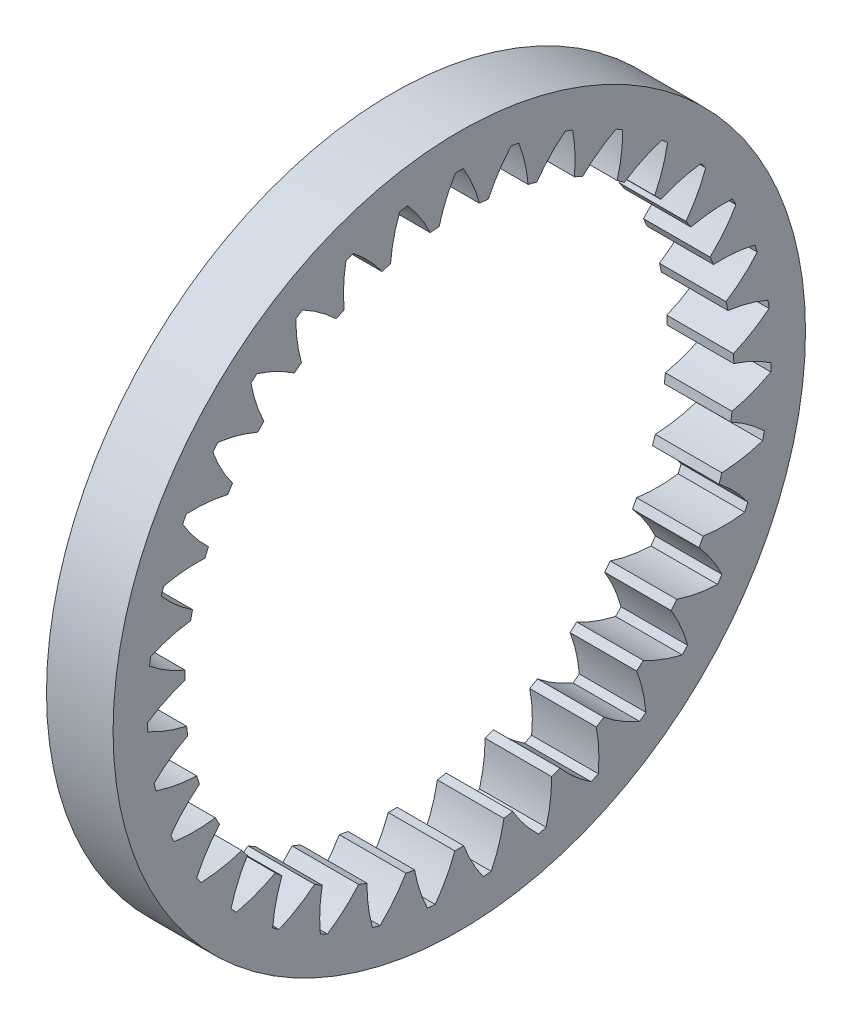
SolidWorks part; units mm, degrees
ref_plane "Plane1" through (0, 0, 0) normal (0, 0, 1) x (1, 0, 0)
ref_plane "Plane2" through (0, 0, 0) normal (0, 1, 0) x (1, 0, 0)
ref_plane "Plane3" through (0, 0, 0) normal (1, 0, 0) x (0, 0, -1)
sketch "HoldingSke" plane through (0, 0, 0) normal (0, 1, 0) x (1, 0, 0)
  line L0 (0, 0) -> (0.3277, -0.2294)
  line L1 (-15, 0) -> (100, 0) construction
  line L2 (0, 0) -> (-2.1039, 2.3779)
  line L3 (0, 0) -> (-11.863, 4.5341)
  line L4 (0, 0) -> (7.0742, 4.9534)
  line L5 (0, 0) -> (-23.7986, -8.8762)
  line L6 (0, 0) -> (-10.5278, -7.1032)
  line L7 (-2.1039, 2.3779) -> (3.3635, 27.1825)
  line L8 (-76.2, 4.8779) -> (-54.61, 4.8779)
  line L9 (-71.009, 38.7566) -> (-53.1078, 45.2721)
  line L10 (-76.2, 71.12) -> (104.1128, 71.12)
  line L11 (0, 0) -> (-10, 0)
  line L12 (-76.2, 101.6) -> (-76.113, 101.6)
  line L13 (24.9733, 27.94) -> (52.9518, 28.4284)
  line L14 (24.9733, 27.94) -> (24.9743, 27.94)
  line L15 (24.9733, 27.94) -> (100.4006, 29.5858)
  circle A0 centre (0, 0) radius 52
  circle A1 centre (0, 0) radius 12.7
  circle A2 centre (0, 0) radius 12.7
  dimension "Num_teeth" = 35
  dimension "Pitch_radius" = 180.3128
  dimension "Width" = 10
  dimension "Diameter" = 104
sketch "BasProSke" plane through (0, 0, 0) normal (0, 1, 0) x (1, 0, 0)
  line L0 (-10, 0) -> (60, 0) construction
  line L1 (0, 41.25) -> (0, 52)
  line L2 (0, 41.25) -> (10, 41.25)
  line L3 (10, 41.25) -> (10, 52)
  line L4 (10, 52) -> (0, 52)
  dimension "Thickness" = 10
  dimension "Diameter" = 104
revolve "Base-Revolve" add sketch "BasProSke" angle 360 about L0
sketch "TooCutSke" plane through (0, 0, 0) normal (1, 0, 0) x (0, 0, -1)
  line L3 (2.1803, 43.6956) -> (2.1803, 53.6633) construction
  line L4 (0, 0) -> (0, 59.563) construction
  line L5 (0, 0) -> (-6.1248, 68.0524) construction
  line L6 (-18.1095, 35.5201) -> (34.3738, 40.2436) construction
  circle A0 centre (0, 0) radius 43.75 construction
  circle A1 centre (0, 0) radius 46.876 construction
  circle A2 centre (0, 0) radius 37.0004 construction
  circle A3 centre (0, 0) radius 41.2246 construction
  arc A4 (3.0386, 41.1125) -> (0.5893, 46.8723) centre (-18.1095, 35.5201) ccw
  arc A5 (3.0386, 41.1125) -> (-3.0386, 41.1125) centre (0, 0) ccw
  arc A6 (0.5893, 46.8723) -> (-0.5893, 46.8723) centre (0, 0) ccw
  arc A7 (-0.5893, 46.8723) -> (-3.0386, 41.1125) centre (18.1095, 35.5201) ccw
extrude "ToothCut" cut sketch "TooCutSke" along normal through all
fillet "Breaks" [suppressed] radius 0.25
fillet "RootFillets" [suppressed] radius 0.626
pattern_circular "TeethCuts" count 35 every 10.286 about axis through (-10, 0, 0) along (1, 0, 0) of "RootFillets", "Breaks", "ToothCut"
equation "' \"Module@HoldingSke\" = 6.35"
equation "' \"Num_teeth@HoldingSke\" = 24"
equation "' \"Ap@HoldingSke\" =  14.5"
equation "' \"Ap@HoldingSke\" = 14.5"
equation "' \"Width@HoldingSke\" = 12"
equation "' \"Diameter@HoldingSke\" = 8 * 25.4"
equation "' \"Show_teeth@HoldingSke\" = 100"
equation "' \"Backlash@HoldingSke\" = 0.009 * 25.4"
equation "' \"Addendum_fac@HoldingSke\" = 1.0"
equation "' \"Dedendum_fac@HoldingSke\" = 1.25"
equation "' \"Dedendum_add@HoldingSke\" = 0.00005 * 25.4"
equation "' \"Clearance_fac@HoldingSke\" = 0.25"
equation "\"Pitch@HoldingSke\" = 1 / \"Module@HoldingSke\" "
equation "\"Overcut_dia@TooCutSke\" = (\"Num_teeth@HoldingSke\" - 2 * \"Addendum_fac@HoldingSke\") / \"Pitch@HoldingSke\" - 0.002 * 25.4"
equation "\"Pitch_dia@TooCutSke\" = \"Num_teeth@HoldingSke\" / \"Pitch@HoldingSke\""
equation "\"Base_dia@TooCutSke\" = \"Num_teeth@HoldingSke\" / \"Pitch@HoldingSke\" * cos((\"Ap@HoldingSke\"  * 3.14159265 / 180)) * 0.90"
equation "\"Root_dia@TooCutSke\" = \"Num_teeth@HoldingSke\"  / \"Pitch@HoldingSke\" + 2 *  \"Dedendum_fac@HoldingSke\"/ \"Pitch@HoldingSke\" + \"Dedendum_add@HoldingSke\" * 2"
equation "\"Half_ang@TooCutSke\" = 180 / \"Num_teeth@HoldingSke\""
equation "\"Half_CT@TooCutSke\" = \"Num_teeth@HoldingSke\" / \"Pitch@HoldingSke\" * sin((3.14159265 / 2 / \"Num_teeth@HoldingSke\")) / 2 + 10 * \"Backlash@HoldingSke\" / 4"
equation "\"Flank_rad@TooCutSke\" = \"Num_teeth@HoldingSke\" / \"Pitch@HoldingSke\" / 4"
equation "\"Radius@RootFillets\"= \"Clearance_fac@HoldingSke\" / \"Pitch@HoldingSke\" + \"Dedendum_add@HoldingSke\""
equation "\"Break_rad@Breaks\" = 0.02 / \"Pitch@HoldingSke\" * 5"
equation "\"Num_teeth@TeethCuts\" = int( \"Show_teeth@HoldingSke\" ) + 1"
equation "\"Num_teeth@TeethCuts\" = ((sgn( \"Num_teeth@TeethCuts\" - \"Num_teeth@HoldingSke\" )-1)*( \"Num_teeth@TeethCuts\" - \"Num_teeth@HoldingSke\" ))/-2+ \"Num_teeth@HoldingSke\""
equation "\"Num_teeth@TeethCuts\" = ((sgn( \"Num_teeth@TeethCuts\" - 2.0)+1)*( \"Num_teeth@TeethCuts\" - 2.0))/2 +2.0"
equation "\"Angle@TeethCuts\" = 360.0 / \"Num_teeth@HoldingSke\""
equation "\"Diameter@BasProSke\" = \"Num_teeth@HoldingSke\"  / \"Pitch@HoldingSke\" + 2 *  \"Dedendum_fac@HoldingSke\"/ \"Pitch@HoldingSke\" + \"Dedendum_add@HoldingSke\" * 2 + 0.002 * 25.4"
equation "\"Diameter@BasProSke\" = ((sgn( \"Diameter@BasProSke\"  - \"Diameter@HoldingSke\" )+1)*( \"Diameter@BasProSke\"  - \"Diameter@HoldingSke\" ))/2 + \"Diameter@HoldingSke\""
equation "\"Inside_diameter@BasProSke\" =  (\"Num_teeth@HoldingSke\" - 2 * \"Addendum_fac@HoldingSke\") / \"Pitch@HoldingSke\" "
equation "\"Thickness@BasProSke\"  = \"Width@HoldingSke\""
